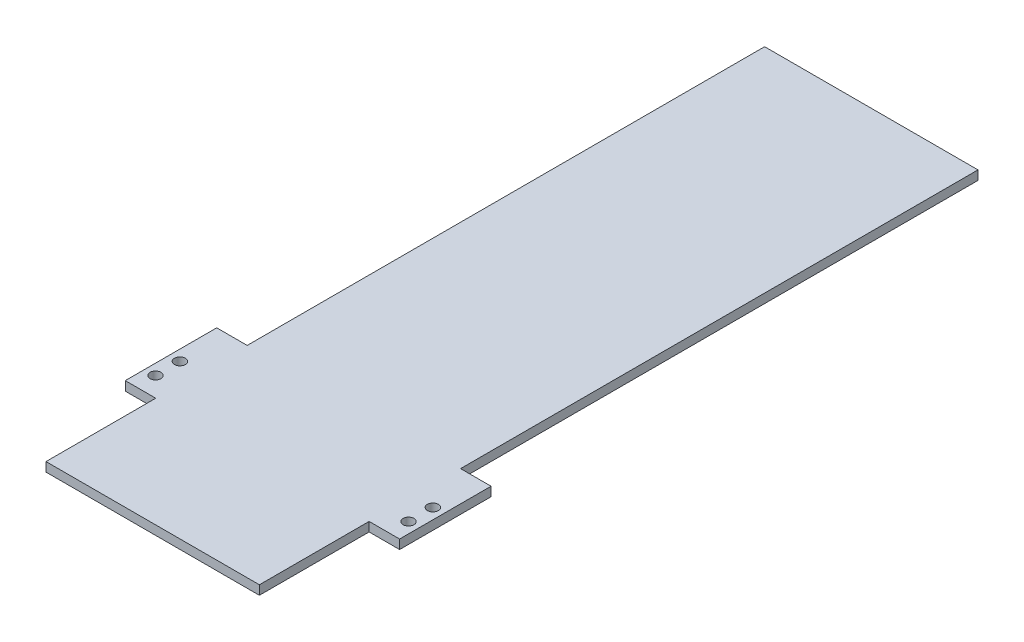
SolidWorks part; units mm, degrees
ref_plane "Front Plane" through (0, 0, 0) normal (0, 0, 1) x (1, 0, 0)
ref_plane "Top Plane" through (0, 0, 0) normal (0, 1, 0) x (1, 0, 0)
ref_plane "Right Plane" through (0, 0, 0) normal (1, 0, 0) x (0, 0, -1)
sketch "Sketch5" plane through (0, 0, 0) normal (0, 1, 0) x (1, 0, 0)
  line L0 (70, 36) -> (80, 36)
  line L1 (0, 0) -> (70, 0)
  line L2 (0, 0) -> (0, 235.74)
  line L3 (0, 235.74) -> (70, 235.74)
  line L4 (70, 0) -> (70, 235.74)
  line L5 (80, 36) -> (80, 66)
  line L6 (80, 66) -> (70, 66)
  line L7 (35, 235.74) -> (35, 0) construction
  line L8 (-10, 66) -> (0, 66)
  line L9 (-10, 36) -> (-10, 66)
  line L10 (0, 36) -> (-10, 36)
  dimension "D1" = 235.74
  dimension "D2" = 70
  dimension "D3" = 36
  dimension "D4" = 30
  dimension "D5" = 10
extrude "Boss-Extrude5" add sketch "Sketch5" along normal blind 3 contours L10 L2 L8 L9 | L7 L3 L2 L1 | L3 L7 L1 L4 | L5 L6 L4 L0 region at (75, 0, -51) region at (52.5, 0, -117.87) region at (17.5, 0, -117.87) region at (-5, 0, -51)
sketch "Sketch6" plane through (0, 3, 0) normal (0, 1, 0) x (1, 0, 0)
  point P0 (76.5, 50.42)
  point P3 (76.5, 42.42)
hole_wizard "M3 Clearance Hole1" positions "Sketch6" profile "Sketch7" hole size "M3" standard "ANSI Metric" end condition through all
sketch "Sketch7" plane through (76.5, 3, -50.42) normal (1, 0, 0) x (0, 0, 1)
  line L0 (0, 0) -> (0, 3)
  line L1 (0, 3) -> (1.8, 3)
  line L2 (1.8, 3) -> (1.8, 0)
  line L5 (1.8, 0) -> (0, 0)
  line L11 (0, -6.35) -> (0, 107.95) construction
  dimension "Thru Hole Dia." = 3.6
  dimension "Thru Hole Depth" = 3
ref_plane "Plane1" through (35, 0, 0) normal (-1, 0, 0) x (0, 0, 1)
mirror "Mirror1" about plane through (35, 0, 0) normal (-1, 0, 0) of "M3 Clearance Hole1"
